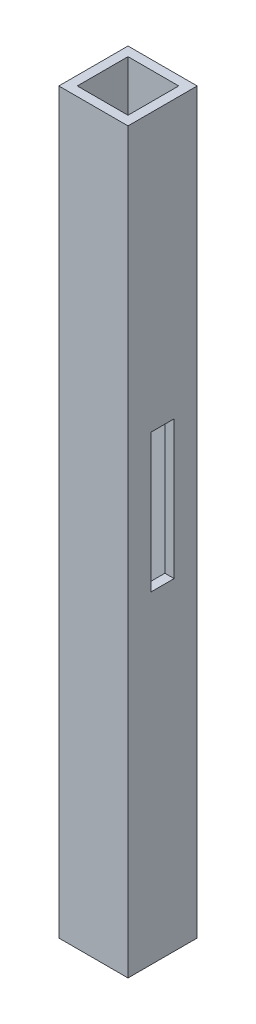
SolidWorks part; units mm, degrees
material "Plain Carbon Steel"
ref_plane "Front Plane" through (0, 0, 0) normal (0, 0, 1) x (1, 0, 0)
ref_plane "Top Plane" through (0, 0, 0) normal (0, 1, 0) x (1, 0, 0)
ref_plane "Right Plane" through (0, 0, 0) normal (1, 0, 0) x (0, 0, -1)
sketch "Sketch2" plane through (0, 0, 0) normal (0, 1, 0) x (1, 0, 0)
  line L1 (0, 0) -> (15, 0)
  line L2 (0, 0) -> (0, 15)
  line L3 (0, 15) -> (15, 15)
  line L4 (15, 0) -> (15, 15)
  dimension "D1" = 15
  dimension "D2" = 15
extrude "Extrude-Thin1" add sketch "Sketch2" along normal blind 160 thin thin type one direction reverse wall 2
sketch "Sketch3" plane through (15, 0, 0) normal (1, 0, 0) x (0, 0, -1)
  line L0 (7.5, 0) -> (7.5, 160) construction
  line L3 (0, 0) -> (15, 0) construction
  line L4 (5, 100) -> (10, 100)
  line L5 (5, 100) -> (5, 70)
  line L6 (5, 70) -> (10, 70)
  line L7 (10, 100) -> (10, 70)
  line L8 (0, 160) -> (15, 160) construction
  point P10 (7.5, 100)
  dimension "D1" = 5
  dimension "D2" = 30
  dimension "D3" = 70
extrude "Cut-Extrude1" cut sketch "Sketch3" against normal through all
ref_axis "Axis1" through (7.5, 0, -2) along (0, 0, -1)
